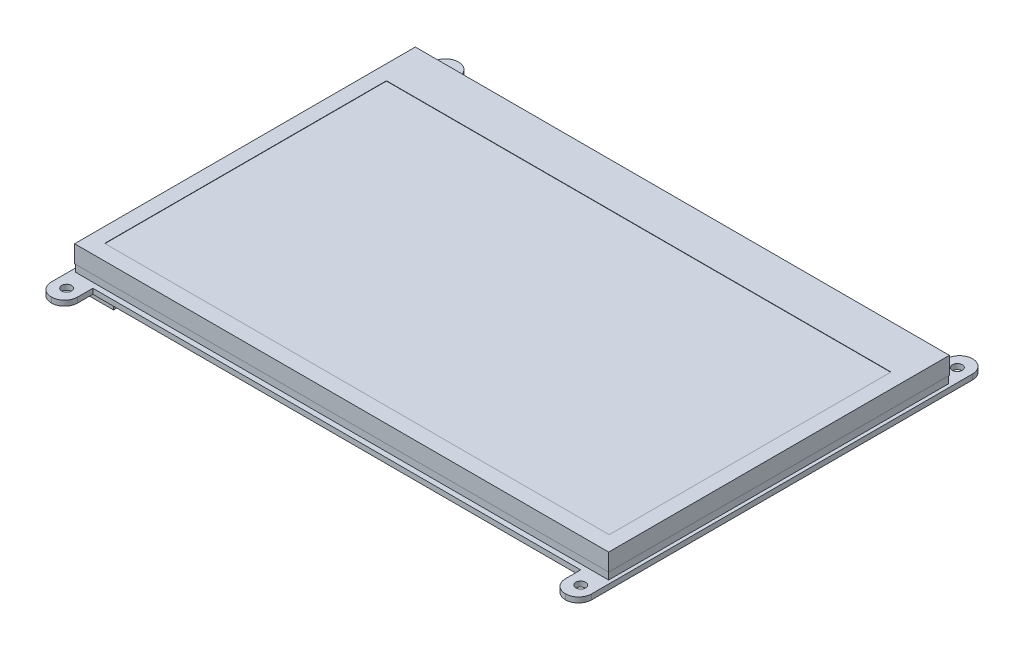
SolidWorks part; units mm, degrees
ref_plane "前视基准面" through (0, 0, 0) normal (0, 0, 1) x (1, 0, 0)
ref_plane "上视基准面" through (0, 0, 0) normal (0, 1, 0) x (1, 0, 0)
ref_plane "右视基准面" through (0, 0, 0) normal (1, 0, 0) x (0, 0, -1)
sketch "草图1" plane through (0, 0, 0) normal (0, 1, 0) x (1, 0, 0)
  line L1 (82.45, -62.135) -> (-82.45, -62.135)
  line L2 (82.45, -62.135) -> (82.45, 62.135)
  line L3 (82.45, 62.135) -> (-82.45, 62.135)
  line L4 (-82.45, -62.135) -> (-82.45, 62.135)
  line L5 (82.45, -62.135) -> (-82.45, 62.135) construction
  line L6 (82.45, 62.135) -> (-82.45, -62.135) construction
  point P0 (0, 0)
  dimension "D1" = 164.9
  dimension "D2" = 124.27
extrude "凸台-拉伸2" add sketch "草图1" along normal blind 1.6
sketch "草图2" plane through (0, 1.6, 0) normal (0, 1, 0) x (1, 0, 0)
  line L0 (82.45, 62.135) -> (-82.45, 62.135) construction
  line L1 (-74.45, 62.135) -> (74.45, 62.135)
  line L2 (-74.45, 62.135) -> (-74.45, 53.48)
  line L3 (-74.45, 53.48) -> (74.45, 53.48)
  line L4 (74.45, 62.135) -> (74.45, 53.48)
  line L5 (0, 0) -> (0, 58.8005) construction
  line L6 (0, 0) -> (23.0464, 0) construction
  line L7 (74.45, -62.135) -> (74.45, -53.48)
  line L8 (-74.45, -53.48) -> (74.45, -53.48)
  line L9 (-74.45, -62.135) -> (-74.45, -53.48)
  line L10 (-74.45, -62.135) -> (74.45, -62.135)
  dimension "D1" = 148.9
  dimension "D2" = 106.96
extrude "切除-拉伸1" cut sketch "草图2" against normal through all
sketch "草图3" plane through (0, 1.6, 0) normal (0, 1, 0) x (1, 0, 0)
  line L1 (81.5, -52) -> (-81.5, -52)
  line L2 (81.5, -52) -> (81.5, 52)
  line L3 (81.5, 52) -> (-81.5, 52)
  line L4 (-81.5, -52) -> (-81.5, 52)
  line L5 (81.5, -52) -> (-81.5, 52) construction
  line L6 (81.5, 52) -> (-81.5, -52) construction
  point P0 (0, 0)
  dimension "D1" = 163
  dimension "D2" = 104
extrude "凸台-拉伸4" add sketch "草图3" along normal blind 7.5
sketch "草图4" plane through (0, 0, 0) normal (0, -1, 0) x (1, 0, 0)
  line L0 (-82.45, -62.135) -> (-82.45, 62.135) construction
  line L1 (-83.45, 49.48) -> (-72.15, 49.48)
  line L2 (-83.45, 49.48) -> (-83.45, 34.18)
  line L3 (-83.45, 34.18) -> (-72.15, 34.18)
  line L4 (-72.15, 49.48) -> (-72.15, 34.18)
  line L5 (74.45, 53.48) -> (-74.45, 53.48) construction
  dimension "D1" = 11.3
  dimension "D2" = 15.3
  dimension "D3" = 4
  dimension "D4" = 10.3
extrude "凸台-拉伸5" add sketch "草图4" along normal blind 5
sketch "草图6" plane through (0, 0, 0) normal (0, -1, 0) x (-1, 0, 0)
  line L0 (82.45, 62.135) -> (82.45, -34.18) construction
  line L1 (47.95, 21.63) -> (44.45, 21.63)
  line L2 (47.95, 21.63) -> (47.95, 31.48)
  line L3 (47.95, 31.48) -> (44.45, 31.48)
  line L4 (44.45, 21.63) -> (44.45, 31.48)
  line L5 (47.95, 21.63) -> (44.45, 31.48) construction
  line L6 (47.95, 31.48) -> (44.45, 21.63) construction
  line L7 (74.45, 53.48) -> (-74.45, 53.48) construction
  point P0 (46.2, 26.555)
  dimension "D1" = 34.5
  dimension "D2" = 3.5
  dimension "D3" = 9.85
  dimension "D4" = 22
extrude "凸台-拉伸6" add sketch "草图6" along normal blind 4.5
fillet "圆角1" radius 1 4 edges at (-46.2, -4.5, -31.48) (-47.95, -4.5, -26.555) (-46.2, -4.5, -21.63) (-44.45, -4.5, -26.555)
fillet "圆角2" radius 1 8 edges at (-47.6571, -4.2071, -31.1871) (-44.7429, -4.2071, -31.1871) (-44.7429, -4.2071, -21.9229) (-47.6571, -4.2071, -21.9229) (-47.95, -1.75, -31.48) (-44.45, -1.75, -31.48) (-44.45, -1.75, -21.63) (-47.95, -1.75, -21.63)
sketch "草图7" plane through (0, 0, 0) normal (0, -1, 0) x (1, 0, 0)
  line L0 (0, 0) -> (0, 50.7237) construction
  line L1 (0, 0) -> (-55.3098, 0) construction
  circle A0 centre (-78.45, 57.48) radius 1.5
  circle A1 centre (78.45, 57.48) radius 1.5
  circle A2 centre (78.45, -57.48) radius 1.5
  circle A3 centre (-78.45, -57.48) radius 1.5
  dimension "D1" = 114.96
  dimension "D2" = 156.9
  dimension "D3" = 3
extrude "切除-拉伸3" cut sketch "草图7" against normal through all
fillet "圆角3" radius 4 8 edges at (-74.45, 0.8, -62.135) (-82.45, 0.8, -62.135) (82.45, 0.8, -62.135) (74.45, 0.8, -62.135) (74.45, 0.8, 62.135) (82.45, 0.8, 62.135) (-74.45, 0.8, 62.135) (-82.45, 0.8, 62.135)
sketch "草图9" plane through (0, 9.1, 0) normal (0, 1, 0) x (1, 0, 0)
  line L1 (77, -47.32) -> (-77, -47.32)
  line L2 (77, -47.32) -> (77, 38.68)
  line L3 (77, 38.68) -> (-77, 38.68)
  line L4 (-77, -47.32) -> (-77, 38.68)
  line L5 (77, -47.32) -> (-77, 38.68) construction
  line L6 (77, 38.68) -> (-77, -47.32) construction
  line L7 (-81.5, -52) -> (81.5, -52) construction
  point P0 (0, -4.32)
  dimension "D1" = 154
  dimension "D2" = 86
  dimension "D3" = 4.68
extrude "切除-拉伸5" cut sketch "草图9" against normal blind 0.1
sketch "草图10" plane through (-83.45, 0, 0) normal (-1, 0, 0) x (0, 0, 1)
  line L0 (49.48, -2.5) -> (46.98, 0)
  line L1 (49.48, -5) -> (49.48, 0) construction
  line L2 (49.48, 0) -> (34.18, 0) construction
  line L3 (46.98, 0) -> (49.48, 0)
  line L4 (49.48, 0) -> (49.48, -2.5)
  line L5 (41.83, -5) -> (41.83, 0) construction
  line L6 (49.48, -5) -> (34.18, -5) construction
  line L7 (34.18, 0) -> (49.48, 0) construction
  line L8 (34.18, 0) -> (34.18, -2.5)
  line L9 (36.68, 0) -> (34.18, 0)
  line L10 (34.18, -2.5) -> (36.68, 0)
extrude "切除-拉伸6" cut sketch "草图10" against normal blind 5
sketch "草图11" plane through (0, 0, 0) normal (0, -1, 0) x (1, 0, 0)
  line L0 (-82.45, -58.135) -> (-82.45, 36.68) construction
  line L1 (-82.55, 27.68) -> (-76.75, 27.68)
  line L2 (-82.55, 27.68) -> (-82.55, 19.88)
  line L3 (-82.55, 19.88) -> (-76.75, 19.88)
  line L4 (-76.75, 27.68) -> (-76.75, 19.88)
  line L5 (-83.45, 34.18) -> (-72.15, 34.18) construction
  line L7 (-82.55, 14.18) -> (-76.75, 14.18)
  line L8 (-82.55, 14.18) -> (-82.55, 6.38)
  line L9 (-82.55, 6.38) -> (-76.75, 6.38)
  line L10 (-76.75, 14.18) -> (-76.75, 6.38)
  dimension "D1" = 7.8
  dimension "D2" = 5.8
  dimension "D3" = 6.5
  dimension "D4" = 5.7
  dimension "D5" = 0.1
extrude "凸台-拉伸7" add sketch "草图11" along normal blind 2.6
sketch "草图12" plane through (0, 0, 0) normal (0, -1, 0) x (1, 0, 0)
  line L0 (-82.45, -58.135) -> (-82.45, 6.38) construction
  line L1 (-74.85, -5.47) -> (-78.45, -5.47)
  line L2 (-74.85, -5.47) -> (-74.85, 3.53)
  line L3 (-74.85, 3.53) -> (-78.45, 3.53)
  line L4 (-78.45, -5.47) -> (-78.45, 3.53)
  line L5 (-74.85, -5.47) -> (-78.45, 3.53) construction
  line L6 (-74.85, 3.53) -> (-78.45, -5.47) construction
  line L7 (-82.55, 6.38) -> (-76.75, 6.38) construction
  point P0 (-76.65, -0.97)
  dimension "D1" = 9
  dimension "D2" = 3.6
  dimension "D3" = 4
  dimension "D4" = 2.85
extrude "凸台-拉伸8" add sketch "草图12" along normal blind 3.5
sketch "草图13" plane through (0, -3.5, 0) normal (0, -1, 0) x (1, 0, 0)
  line L0 (-74.85, -5.47) -> (-74.85, 3.53) construction
  line L1 (-75.9, -2.97) -> (-77.4, -2.97)
  line L2 (-75.9, -2.97) -> (-75.9, 1.03)
  line L3 (-75.9, 1.03) -> (-77.4, 1.03)
  line L4 (-77.4, -2.97) -> (-77.4, 1.03)
  line L5 (-75.9, -2.97) -> (-77.4, 1.03) construction
  line L6 (-75.9, 1.03) -> (-77.4, -2.97) construction
  line L7 (-78.45, -5.47) -> (-74.85, -5.47) construction
  point P0 (-76.65, -0.97)
  point P8 (-74.85, -0.97)
  point P13 (-76.65, -5.47)
  dimension "D1" = 4
  dimension "D2" = 1.5
extrude "切除-拉伸7" cut sketch "草图13" against normal blind 0.1
sketch "草图14" plane through (0, -3.4, 0) normal (0, -1, 0) x (1, 0, 0)
  line L0 (-75.9, -2.97) -> (-75.9, 1.03) construction
  line L1 (-77.4, 1.03) -> (-75.9, 1.03)
  line L2 (-77.4, 1.03) -> (-77.4, -0.97)
  line L3 (-77.4, -0.97) -> (-75.9, -0.97)
  line L4 (-75.9, 1.03) -> (-75.9, -0.97)
extrude "凸台-拉伸9" add sketch "草图14" along normal blind 2
sketch "草图15" plane through (0, 0, 0) normal (0, -1, 0) x (1, 0, 0)
  line L0 (74.45, 53.48) -> (-74.45, 53.48) construction
  line L1 (-21.45, 27.48) -> (-1.65, 27.48)
  line L2 (-21.45, 27.48) -> (-21.45, 13.68)
  line L3 (-21.45, 13.68) -> (-1.65, 13.68)
  line L4 (-1.65, 27.48) -> (-1.65, 13.68)
  line L5 (-21.45, 27.48) -> (-1.65, 13.68) construction
  line L6 (-21.45, 13.68) -> (-1.65, 27.48) construction
  line L7 (-82.45, -58.135) -> (-82.45, 6.38) construction
  point P0 (-11.55, 20.58)
  dimension "D1" = 19.8
  dimension "D2" = 13.8
  dimension "D3" = 26
  dimension "D4" = 61
extrude "凸台-拉伸10" add sketch "草图15" along normal blind 2
sketch "草图16" plane through (0, 1.6, 0) normal (0, 1, 0) x (1, 0, 0)
  line L0 (-81.4, 51.9) -> (-81.4, -51.9)
  line L1 (-81.4, -51.9) -> (81.4, -51.9)
  line L2 (81.4, -51.9) -> (81.4, 51.9)
  line L3 (81.4, 51.9) -> (-81.4, 51.9)
  line L4 (-81.5, 52) -> (-81.5, -52)
  line L5 (-81.5, -52) -> (81.5, -52)
  line L6 (81.5, -52) -> (81.5, 52)
  line L7 (81.5, 52) -> (-81.5, 52)
  line L8 (-81.5, 52) -> (-81.5, -52)
  line L9 (-81.5, -52) -> (81.5, -52)
  line L10 (81.5, -52) -> (81.5, 52)
  line L11 (81.5, 52) -> (-81.5, 52)
  dimension "D1" = 0
  dimension "D2" = 0.1
extrude "切除-拉伸9" cut sketch "草图16" along normal blind 2.2
